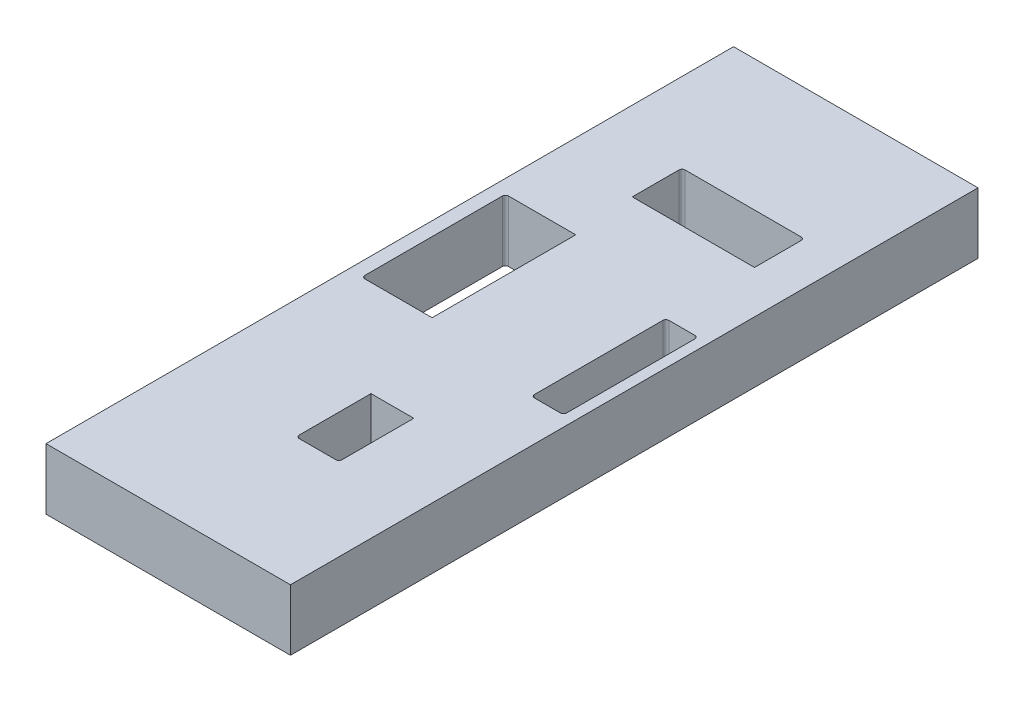
SolidWorks part; units mm, degrees
material "Plain Carbon Steel"
ref_plane "Front Plane" through (0, 0, 0) normal (0, 0, 1) x (1, 0, 0)
ref_plane "Top Plane" through (0, 0, 0) normal (0, 1, 0) x (1, 0, 0)
ref_plane "Right Plane" through (0, 0, 0) normal (1, 0, 0) x (0, 0, -1)
sketch "Sketch1" plane through (0, 0, 0) normal (0, 1, 0) x (1, 0, 0)
  line L0 (-46, 0) -> (34, 0) construction
  line L1 (-46, -112.5) -> (34, -112.5)
  line L2 (-46, -112.5) -> (-46, 112.5)
  line L3 (-46, 112.5) -> (34, 112.5)
  line L4 (34, -112.5) -> (34, 112.5)
  dimension "D1" = 34
  dimension "D2" = 46
  dimension "D3" = 225
extrude "Boss-Extrude1" add sketch "Sketch1" against normal blind 20
sketch "Sketch2" plane through (0, 0, 0) normal (0, 1, 0) x (1, 0, 0)
  line L0 (18, -9.64) -> (29.5, -9.64) construction
  line L1 (29.5, 14.36) -> (18, 14.36) construction
  line L2 (30.5, -8.64) -> (30.5, 13.36) construction
  line L3 (20, -9.64) -> (29.5, -9.64) construction
  line L4 (29.5, 14.36) -> (20, 14.36) construction
  line L5 (30.5, -8.64) -> (30.5, 13.36) construction
  line L6 (20, 14.36) -> (20, -9.64) construction
  line L7 (22, -9.64) -> (22, 14.36) construction
  line L9 (21, -19.64) -> (29.5, -19.64)
  line L10 (20, -18.64) -> (20, 23.36)
  line L11 (21, 24.36) -> (29.5, 24.36)
  line L12 (30.5, -18.64) -> (30.5, 23.36)
  arc A0 (29.5, -9.64) -> (30.5, -8.64) centre (29.5, -8.64) ccw construction
  arc A1 (30.5, 13.36) -> (29.5, 14.36) centre (29.5, 13.36) ccw construction
  arc A2 (29.5, -9.64) -> (30.5, -8.64) centre (29.5, -8.64) ccw construction
  arc A3 (30.5, 13.36) -> (29.5, 14.36) centre (29.5, 13.36) ccw construction
  arc A4 (21, -19.64) -> (20, -18.64) centre (21, -18.64) cw
  arc A5 (29.5, -19.64) -> (30.5, -18.64) centre (29.5, -18.64) ccw
  arc A6 (29.5, 24.36) -> (30.5, 23.36) centre (29.5, 23.36) cw
  arc A7 (20, 23.36) -> (21, 24.36) centre (21, 23.36) cw
  dimension "D6" = 1
  dimension "D1" = 2
  dimension "D2" = 10.5
  dimension "D3" = 24
  dimension "D4" = 10
  dimension "D5" = 10
extrude "Cut-Extrude1" cut sketch "Sketch2" against normal up to next
sketch "Sketch4" plane through (0, 0, 0) normal (0, 1, 0) x (1, 0, 0)
  line L0 (7, -68.64) -> (7, -43.14) construction
  line L2 (-7, -43.14) -> (-7, -68.64) construction
  line L3 (-6, -69.64) -> (6, -69.64) construction
  line L4 (7, -68.64) -> (7, -45.14)
  line L5 (7, -45.14) -> (-7, -45.14)
  line L6 (-7, -45.14) -> (-7, -68.64)
  line L7 (-6, -69.64) -> (6, -69.64)
  line L8 (-7, -47.14) -> (7, -47.14) construction
  arc A2 (-7, -68.64) -> (-6, -69.64) centre (-6, -68.64) ccw construction
  arc A3 (6, -69.64) -> (7, -68.64) centre (6, -68.64) ccw construction
  arc A6 (-7, -68.64) -> (-6, -69.64) centre (-6, -68.64) ccw
  arc A7 (6, -69.64) -> (7, -68.64) centre (6, -68.64) ccw
  dimension "D1" = 2
extrude "Cut-Extrude2" cut sketch "Sketch4" against normal up to next
sketch "Sketch5" plane through (0, 0, 0) normal (0, 1, 0) x (1, 0, 0)
  line L1 (-16.5, 33.36) -> (-40.5, 33.36) construction
  line L2 (-41.5, 32.36) -> (-41.5, -12.64) construction
  line L3 (-40.5, -13.64) -> (-16.5, -13.64) construction
  line L4 (-18.5, -13.64) -> (-18.5, 33.36)
  line L5 (-18.5, 33.36) -> (-40.5, 33.36)
  line L6 (-41.5, 32.36) -> (-41.5, -12.64)
  line L7 (-40.5, -13.64) -> (-18.5, -13.64)
  line L8 (-20.5, 33.36) -> (-20.5, -13.64) construction
  arc A2 (-40.5, 33.36) -> (-41.5, 32.36) centre (-40.5, 32.36) ccw construction
  arc A3 (-41.5, -12.64) -> (-40.5, -13.64) centre (-40.5, -12.64) ccw construction
  arc A6 (-40.5, 33.36) -> (-41.5, 32.36) centre (-40.5, 32.36) ccw
  arc A7 (-41.5, -12.64) -> (-40.5, -13.64) centre (-40.5, -12.64) ccw
  dimension "D1" = 2
extrude "Cut-Extrude3" cut sketch "Sketch5" against normal up to next
sketch "Sketch6" plane through (0, 0, 0) normal (0, 1, 0) x (1, 0, 0)
  line L0 (19, 69.64) -> (-19, 69.64) construction
  line L1 (-20, 68.64) -> (-20, 51.36) construction
  line L3 (20, 51.36) -> (20, 68.64) construction
  line L4 (19, 69.64) -> (-19, 69.64)
  line L5 (-20, 68.64) -> (-20, 53.36)
  line L6 (-20, 53.36) -> (20, 53.36)
  line L7 (20, 53.36) -> (20, 68.64)
  line L8 (-20, 55.36) -> (20, 55.36) construction
  arc A0 (20, 68.64) -> (19, 69.64) centre (19, 68.64) ccw construction
  arc A1 (-19, 69.64) -> (-20, 68.64) centre (-19, 68.64) ccw construction
  arc A4 (20, 68.64) -> (19, 69.64) centre (19, 68.64) ccw
  arc A5 (-19, 69.64) -> (-20, 68.64) centre (-19, 68.64) ccw
  dimension "D1" = 2
extrude "Cut-Extrude4" cut sketch "Sketch6" against normal up to next
